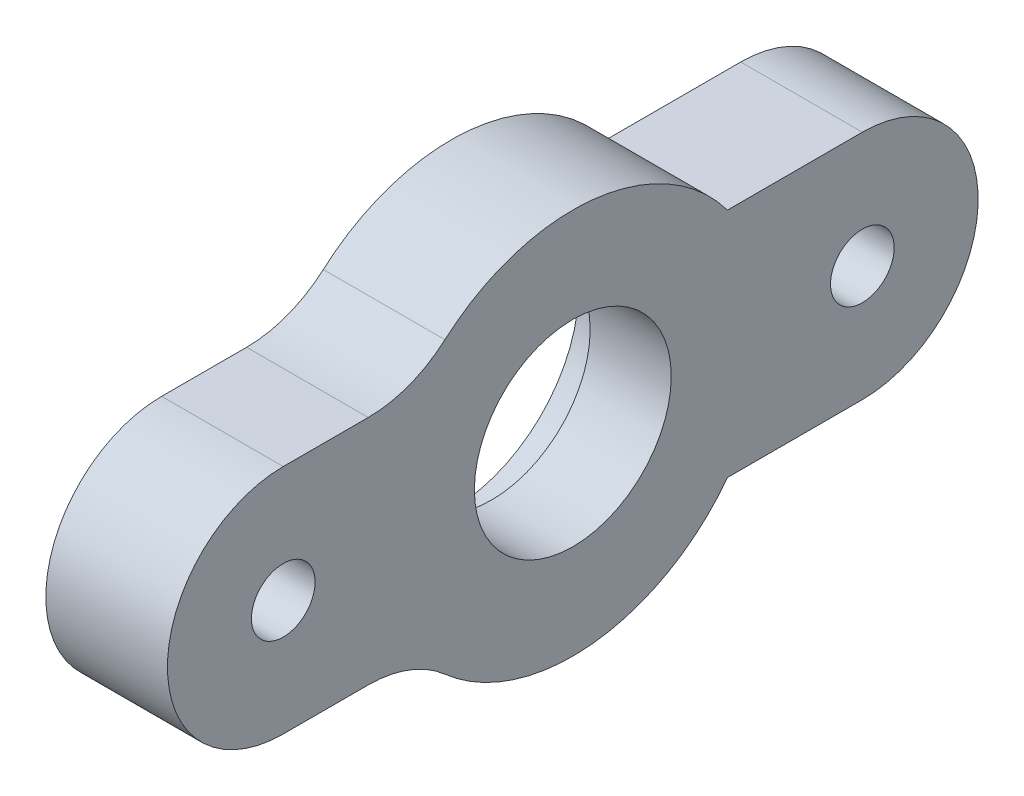
SolidWorks part; units mm, degrees
ref_plane "Ebene vorne" through (0, 0, 0) normal (0, 0, 1) x (1, 0, 0)
ref_plane "Ebene oben" through (0, 0, 0) normal (0, 1, 0) x (1, 0, 0)
ref_plane "Ebene rechts" through (0, 0, 0) normal (1, 0, 0) x (0, 0, -1)
sketch "Skizze4" plane through (0, 0, 0) normal (0, 0, 1) x (1, 0, 0)
  line L0 (0, 11) -> (3.5, 11)
  line L1 (0, 11) -> (0, 16.6831)
  line L2 (0, 16.6831) -> (10.5, 16.6831)
  line L3 (10.5, 16.6831) -> (10.5, 8.5)
  line L4 (10.5, 8.5) -> (3.5, 8.5)
  line L5 (3.5, 8.5) -> (3.5, 11)
  line L6 (0, 0) -> (13.1594, 0) construction
  dimension "D1" = 11
  dimension "D2" = 3.5
  dimension "D3" = 2.5
  dimension "D4" = 7
revolve "Rotation1" add sketch "Skizze4" angle 360 about L6
sketch "Skizze5" plane through (10.5, 0, 0) normal (1, 0, 0) x (0, 0, -1)
  line L0 (-25, 0) -> (25, 0) construction
  line L1 (-25, 0) -> (25, 0) construction
  line L2 (-25, 10) -> (-13.3538, 10)
  line L3 (-25, -10) -> (-13.3538, -10)
  arc A3 (-25, 10) -> (-25, -10) centre (-25, 0) ccw
  arc A5 (-13.3538, 10) -> (-13.3538, -10) centre (0, 0) ccw
  circle A6 centre (0, 0) radius 16.6831 construction
  arc A7 (13.3538, 10) -> (13.3538, -10) centre (0, 0) ccw
  point P0 (0, 0)
  point P4 (0, 0)
  point P16 (-25, 0)
  dimension "D2" = 20
  dimension "D1" = 50
extrude "Aufsatz-Linear austragen1" add sketch "Skizze5" against normal blind 10.5 contours L3 A5 L2 A3
hole_wizard "Ø5.5 (5.5) Durchmesser Bohrung1" positions "Skizze6" profile "Skizze7" hole size "Ø5.5" standard "ISO" end condition through all
sketch "Skizze6" plane through (10.5, 0, 0) normal (1, 0, 0) x (0, 0, -1)
  point P0 (-25, 0)
sketch "Skizze7" plane through (10.5, 0, 25) normal (0, 1, 0) x (0, 0, -1)
  line L0 (0, 0) -> (0, 10.5)
  line L1 (0, 10.5) -> (2.75, 10.5)
  line L2 (2.75, 10.5) -> (2.75, 0)
  line L5 (2.75, 0) -> (0, 0)
  line L11 (0, -6.35) -> (0, 107.95) construction
  dimension "Bohrerdurchmesser" = 5.5
  dimension "Bohrungstiefe" = 10.5
mirror "Spiegeln1" about plane through (0, 0, 0) normal (0, 0, 1) of "Ø5.5 (5.5) Durchmesser Bohrung1", "Aufsatz-Linear austragen1"
fillet "Verrundung2" radius 10 2 edges at (5.25, -10, 13.3538) (5.25, 10, 13.3538)
